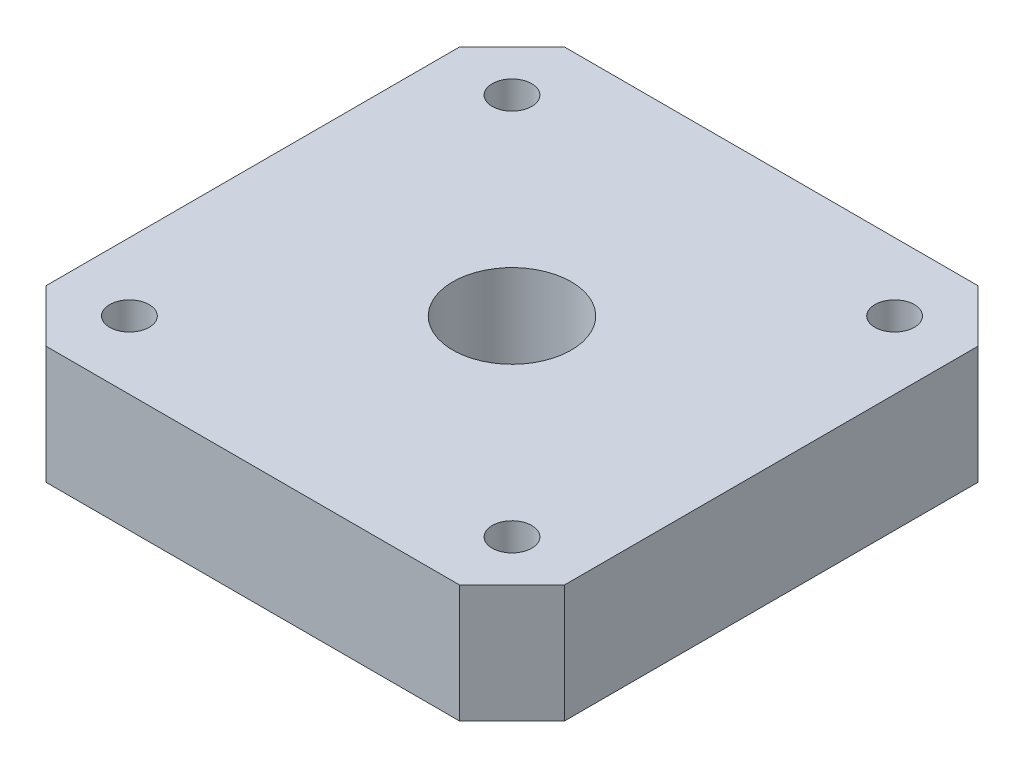
SolidWorks part; units mm, degrees
ref_plane "Plano frontal" through (0, 0, 0) normal (0, 0, 1) x (1, 0, 0)
ref_plane "Plano superior" through (0, 0, 0) normal (0, 1, 0) x (1, 0, 0)
ref_plane "Plano direito" through (0, 0, 0) normal (1, 0, 0) x (0, 0, -1)
sketch "Esboço1" plane through (0, 0, 0) normal (0, 1, 0) x (1, 0, 0)
  line L1 (-21, -21) -> (21, -21)
  line L2 (-21, -21) -> (-21, 21)
  line L3 (-21, 21) -> (21, 21)
  line L4 (21, -21) -> (21, 21)
  line L5 (-21, -21) -> (21, 21) construction
  line L6 (-21, 21) -> (21, -21) construction
  point P0 (0, 0)
  dimension "D1" = 42
  dimension "D2" = 42
base flange "Flange-base1" sketch "Esboço1" thickness 9.55 reverse thickness direction no parameters "D1"=10
sketch "Esboço3" plane through (0, -9.55, 0) normal (0, -1, 0) x (1, 0, 0)
  line L0 (-21, 16.7574) -> (-16.7574, 21)
  line L1 (-16.7574, 21) -> (-21, 21)
  line L2 (-21, 21) -> (-21, 16.7574)
  line L3 (-21, -21) -> (-21, -16.7574)
  line L4 (-21, -16.7574) -> (-16.7574, -21)
  line L5 (-16.7574, -21) -> (-21, -21)
  line L6 (21, -21) -> (21, -16.7574)
  line L7 (21, -16.7574) -> (16.7574, -21)
  line L8 (16.7574, -21) -> (21, -21)
  line L9 (21, 16.7574) -> (21, 21)
  line L10 (21, 21) -> (16.7574, 21)
  line L11 (16.7574, 21) -> (21, 16.7574)
extrude "Corte-extrusão2" cut sketch "Esboço3" against normal through all normal cut yes
sketch "Esboço4" plane through (0, -9.55, 0) normal (0, -1, 0) x (1, 0, 0)
  line L8 (21, 16.7574) -> (16.7574, 21)
  line L9 (16.7574, 21) -> (-16.7574, 21)
  line L10 (-16.7574, 21) -> (-21, 16.7574)
  line L11 (-21, 16.7574) -> (-21, -16.7574)
  line L12 (-21, -16.7574) -> (-16.7574, -21)
  line L13 (-16.7574, -21) -> (16.7574, -21)
  line L14 (16.7574, -21) -> (21, -16.7574)
  line L15 (21, -16.7574) -> (21, 16.7574)
  line L16 (21, 16.7574) -> (16.7574, 21)
  line L17 (16.7574, 21) -> (-16.7574, 21)
  line L18 (-16.7574, 21) -> (-21, 16.7574)
  line L19 (-21, 16.7574) -> (-21, -16.7574)
  line L20 (-21, -16.7574) -> (-16.7574, -21)
  line L21 (-16.7574, -21) -> (16.7574, -21)
  line L22 (16.7574, -21) -> (21, -16.7574)
  line L23 (21, -16.7574) -> (21, 16.7574)
  circle A0 centre (0, 0) radius 4.8 construction
  circle A1 centre (-15.5, -15.5) radius 1.25 construction
  circle A2 centre (15.5, -15.5) radius 1.25 construction
  circle A3 centre (15.5, 15.5) radius 1.25 construction
  circle A4 centre (-15.5, 15.5) radius 1.25 construction
  circle A5 centre (0, 0) radius 4.8
  circle A6 centre (-15.5, -15.5) radius 1.25
  circle A7 centre (15.5, -15.5) radius 1.25
  circle A8 centre (15.5, 15.5) radius 1.25
  circle A9 centre (-15.5, 15.5) radius 1.25
  dimension "D1" = 0
extrude "Corte-extrusão4" cut sketch "Esboço4" against normal through all contours A5 normal cut yes
sketch "Esboço16" plane through (0, -9.55, 0) normal (0, -1, 0) x (1, 0, 0)
  circle A0 centre (-15.5, -15.5) radius 2
  circle A1 centre (-15.5, 15.5) radius 2
  circle A2 centre (15.5, 15.5) radius 2
  circle A3 centre (15.5, -15.5) radius 2
extrude "Corte-extrusão6" cut sketch "Esboço16" against normal blind 3 normal cut yes
sketch "Esboço19" plane through (0, -6.55, 0) normal (0, -1, 0) x (1, 0, 0)
  circle A0 centre (15.5, -15.5) radius 1.6 construction
  circle A1 centre (-15.5, -15.5) radius 1.6 construction
  circle A2 centre (15.5, 15.5) radius 1.6 construction
  circle A3 centre (-15.5, 15.5) radius 1.6 construction
  circle A4 centre (15.5, -15.5) radius 1.6
  circle A5 centre (-15.5, -15.5) radius 1.6
  circle A6 centre (15.5, 15.5) radius 1.6
  circle A7 centre (-15.5, 15.5) radius 1.6
extrude "Corte-extrusão7" cut sketch "Esboço19" against normal through all normal cut yes
sketch "Curva-Linhas1" [suppressed] plane through (0, 0, 0) normal (0, 1, 0) x (1, 0, 0)
sketch "Caixa delimitadora1" [suppressed] plane through (0, 0, 0) normal (0, 1, 0) x (1, 0, 0)
sheet metal parameters "Chapa metálica1" thickness 9.55 parameters "D1"=10
flat pattern "Padrão-Plano1" [suppressed]
sketch "Curva-Linhas2" plane through (0, 0, 0) normal (0, 1, 0) x (1, 0, 0)
sketch3d "Caixa delimitadora2" [suppressed]
  line L0 (-21, -21, 0) -> (-21, 21, 0) construction
  line L1 (21, -21, 0) -> (21, 21, 0) construction
  line L2 (-21, -21, 0) -> (21, -21, 0) construction
  line L3 (-21, 21, 0) -> (21, 21, 0) construction
sheet metal parameters "Chapa metálica3" thickness 9.55 parameters "D1"=10
flat pattern "Padrão-Plano1"
sketch "Curva-Linhas2" plane through (0, 0, 0) normal (0, 1, 0) x (1, 0, 0)
sketch3d "Caixa delimitadora2" [suppressed]
  line L0 (-21, -21, 0) -> (-21, 21, 0) construction
  line L1 (21, -21, 0) -> (21, 21, 0) construction
  line L2 (-21, -21, 0) -> (21, -21, 0) construction
  line L3 (-21, 21, 0) -> (21, 21, 0) construction
sheet metal parameters "Chapa metálica9" thickness 9.55 parameters "D1"=10
flat pattern "Padrão-Plano1"
sketch "Curva-Linhas2" plane through (0, 0, 0) normal (0, 1, 0) x (1, 0, 0)
sketch3d "Caixa delimitadora2" [suppressed]
  line L0 (-21, -21, 0) -> (-21, 21, 0) construction
  line L1 (21, -21, 0) -> (21, 21, 0) construction
  line L2 (-21, -21, 0) -> (21, -21, 0) construction
  line L3 (-21, 21, 0) -> (21, 21, 0) construction
sheet metal parameters "Chapa metálica11" thickness 9.55 parameters "D1"=10
flat pattern "Padrão-Plano1"
sketch "Curva-Linhas2" plane through (0, 0, 0) normal (0, 1, 0) x (1, 0, 0)
sketch3d "Caixa delimitadora2" [suppressed]
  line L0 (-21, -21, 0) -> (-21, 21, 0) construction
  line L1 (21, -21, 0) -> (21, 21, 0) construction
  line L2 (-21, -21, 0) -> (21, -21, 0) construction
  line L3 (-21, 21, 0) -> (21, 21, 0) construction
sheet metal parameters "Chapa metálica12" thickness 9.55 parameters "D1"=10
flat pattern "Padrão-Plano1"
sketch "Curva-Linhas2" plane through (0, 0, 0) normal (0, 1, 0) x (1, 0, 0)
sketch3d "Caixa delimitadora2" [suppressed]
  line L0 (21, 21, 0) -> (-21, 21, 0) construction
  line L1 (21, -21, 0) -> (-21, -21, 0) construction
  line L2 (21, 21, 0) -> (21, -21, 0) construction
  line L3 (-21, 21, 0) -> (-21, -21, 0) construction
